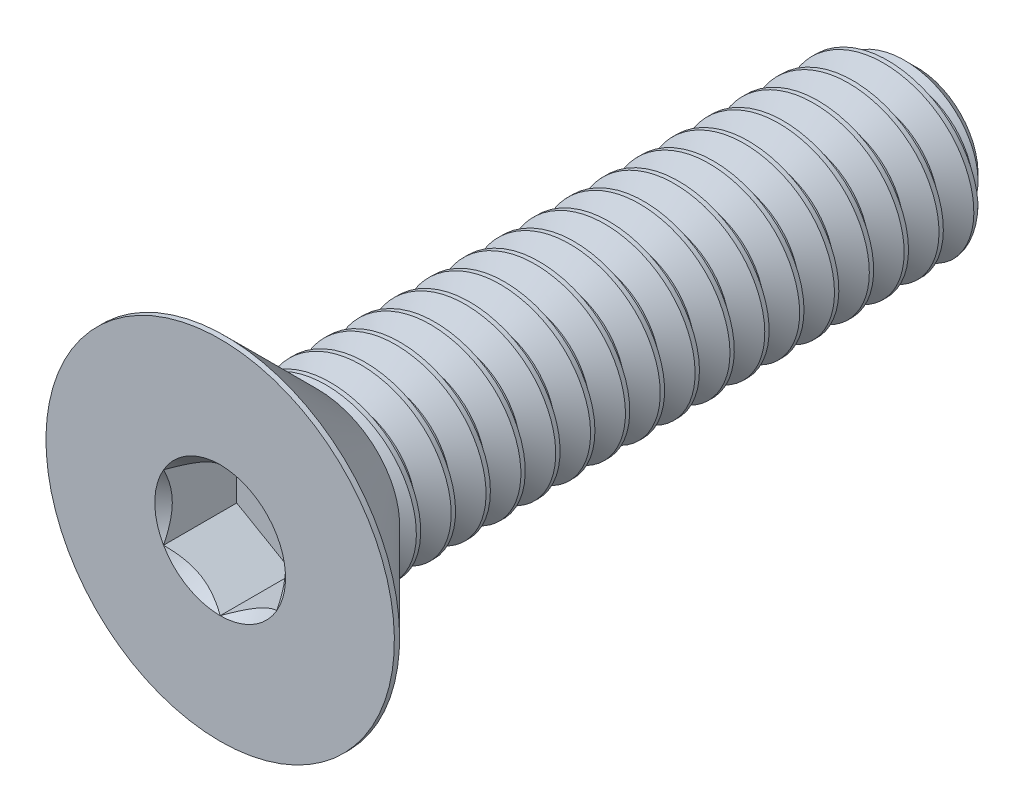
SolidWorks part; units mm, degrees
ref_plane "Front" through (0, 0, 0) normal (0, 0, 1) x (1, 0, 0)
ref_plane "Top" through (0, 0, 0) normal (0, 1, 0) x (1, 0, 0)
ref_plane "Right" through (0, 0, 0) normal (1, 0, 0) x (0, 0, -1)
sketch "Sketch11" plane through (0, 0, 0) normal (1, 0, 0) x (0, 0, -1)
  line L0 (-4, 2) -> (4, 2) construction
  line L5 (-4, 2) -> (-4, -2) construction
  line L6 (4, 1) -> (4, -1) construction
  line L7 (-3.99, 0.65) -> (-3.99, -0.65) construction
  line L8 (3.975, 1.0433) -> (4.375, 1.0433) construction
  line L9 (4.375, 1.0433) -> (4.175, 0.6969) construction
  line L10 (4.175, 0.6969) -> (3.975, 1.0433) construction
  line L11 (4.15, 0.7402) -> (4.2, 0.7402) construction
  line L12 (4.175, 0.7402) -> (4.175, 0.6969) construction
  line L13 (3.9875, 1.0217) -> (4.3625, 1.0217) construction
  line L14 (4.175, 1.0433) -> (4.175, 1) construction
  line L15 (4, 1) -> (4.35, 1) construction
  line L17 (-3.94, 2) -> (-1.94, 0) construction
  line L18 (-1.94, 0) -> (-3.94, -2) construction
  point P3 (-2.8, 2)
  point P8 (0, 2)
  point P21 (4.175, 1.0217)
  point P26 (-4, 0)
  point P28 (-3.99, 0)
  point P29 (4, 0)
  dimension "Length" = 8
  dimension "Head Diameter" = 4
  dimension "Thread Major Diameter" = 2
  dimension "Head Height" = 1.2
  dimension "Drive Size" = 1.3
  dimension "Thread Pitch" = 0.4
  dimension "D1" = 0.05
  dimension "D2" = 0.01
  dimension "D3" = 0.06
  dimension "Countersink Angle" = 90
sketch "Sketch1" plane through (0, 0, 0) normal (1, 0, 0) x (0, 0, -1)
  line L2 (-2.8, 1) -> (4, 1)
  line L3 (4, 1) -> (4, 0)
  line L4 (-3.16, 1) -> (-3.16, 0)
  line L5 (-2.8, 1) -> (-3.16, 1)
  line L6 (-4, 2) -> (-4, -2) construction
  line L7 (4, 1) -> (4, -1) construction
  line L8 (-3.16, 0) -> (4, 0)
  dimension "D1" = 0.84
revolve "Revolve1" add sketch "Sketch1" angle 360 mid plane about L8
chamfer "Chamfer1" distance 0.3 angle 45 1 edges at (0, -1, -4)
sketch "Sketch7" plane through (0, 0, 0) normal (1, 0, 0) x (0, 0, -1)
  line L2 (-4, 2) -> (-3.94, 2)
  line L5 (-2.8, 0.86) -> (-2.8, 0)
  line L6 (-4, 2) -> (-4, 0)
  line L8 (-4, 2) -> (-4, -2) construction
  line L9 (-4, 0) -> (-2.8, 0)
  line L12 (-3.94, 2) -> (-2.8, 0.86)
  line L13 (-3.94, 2) -> (-1.94, 0) construction
revolve "Revolve2" add sketch "Sketch7" angle 360 mid plane about L9 region at (0, 0.7698, 3.4817)
ref_plane "Plane1" through (0, 0, 2.8) normal (0, 0, 1) x (1, 0, 0)
sketch "Sketch5" plane through (0, 0, 4) normal (0, 0, 1) x (1, 0, 0)
  line L1 (0.65, -0.3753) -> (0.65, 0.3753)
  line L2 (0.65, 0.3753) -> (0, 0.7506)
  line L3 (0, 0.7506) -> (-0.65, 0.3753)
  line L4 (-0.65, 0.3753) -> (-0.65, -0.3753)
  line L5 (-0.65, -0.3753) -> (0, -0.7506)
  line L6 (0, -0.7506) -> (0.65, -0.3753)
  circle A0 centre (0, 0) radius 0.65 construction
extrude "Cut-Extrude2" cut sketch "Sketch5" against normal blind 0.84
sketch "Sketch6" plane through (0, 0, 4) normal (0, 0, -1) x (-1, 0, 0)
  circle A0 centre (0, 0) radius 0.7506
extrude "Cut-Extrude3" cut sketch "Sketch6" along normal blind 0.84 draft 45
sketch "Sketch12" plane through (0, 0, -4) normal (0, 0, -1) x (-1, 0, 0)
  circle A0 centre (0, 0) radius 1 construction
  circle A1 centre (0, 0) radius 1
curve "Helix/Spiral1" pitch 0.4 height 8 radius 1 centre (0, 0, -4) axis (0, 0, 1) start towards (0, 1, 0)
sketch "Sketch13" plane through (0, 0, 0) normal (1, 0, 0) x (0, 0, -1)
  line L0 (3.9875, 1.0217) -> (4.3625, 1.0217)
  line L1 (4.3625, 1.0217) -> (4.2, 0.7402)
  line L2 (4.2, 0.7402) -> (4.15, 0.7402)
  line L3 (4.15, 0.7402) -> (3.9875, 1.0217)
sweep "Cut-Sweep1" cut profiles "Sketch13" path "Helix/Spiral1" align with end faces yes
combine bodies "Combine1" operation type add bodies to combine 113 127
equation "\"D1@Chamfer1\"=\"Thread Pitch@Sketch11\" * .75"
equation "\"D1@Cut-Extrude2\"= \"Head Height@Sketch11\" * .7"
equation "\"D1@Cut-Extrude3\" = \"D1@Cut-Extrude2\""
equation "\"D1@Sketch11\"=\"Thread Pitch@Sketch11\"/8"
equation "\"D3@Sketch11\"=\"Head Height@Sketch11\"*.05"
equation "\"D4@Helix/Spiral1\"=\"Thread Pitch@Sketch11\""
equation "\"D1@Sketch1\"=\"Head Height@Sketch11\"*.7"
equation "\"D3@Helix/Spiral1\"=\"Length@Sketch11\""
